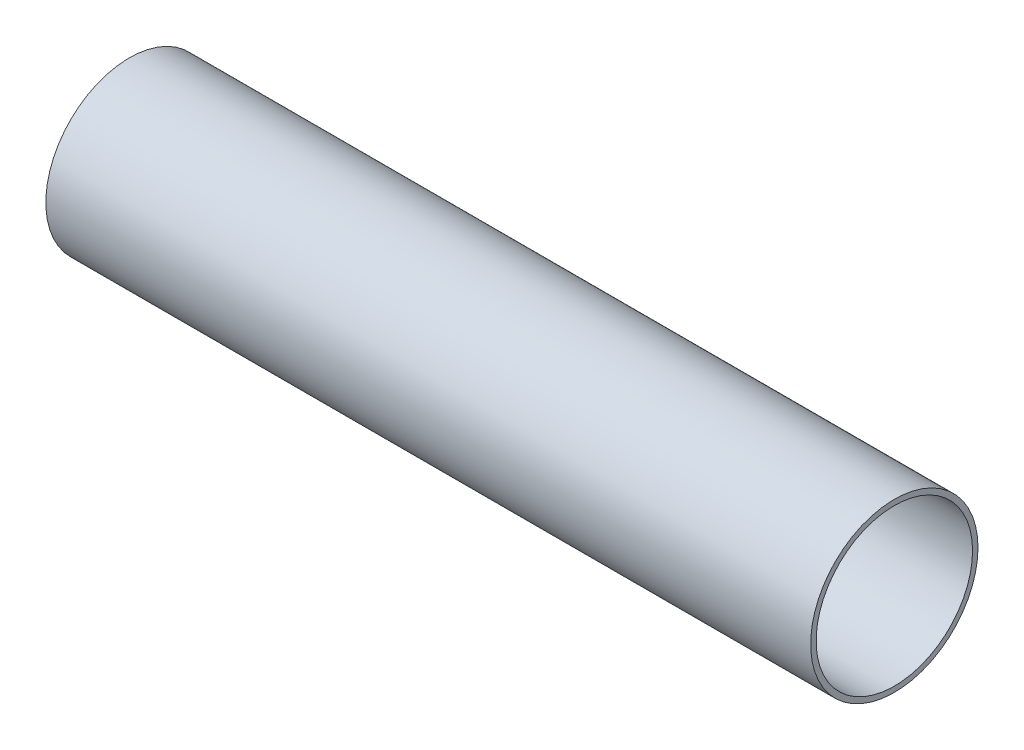
SolidWorks part; units mm, degrees
ref_plane "Front Plane" through (0, 0, 0) normal (0, 0, 1) x (1, 0, 0)
ref_plane "Top Plane" through (0, 0, 0) normal (0, 1, 0) x (1, 0, 0)
ref_plane "Right Plane" through (0, 0, 0) normal (1, 0, 0) x (0, 0, -1)
sketch "Sketch1" plane through (0, 0, 0) normal (1, 0, 0) x (0, 0, -1)
  circle A0 centre (0, 0) radius 45.847
  circle A1 centre (0, 0) radius 42.8625
  dimension "D1" = 91.694
  dimension "D2" = 85.725
extrude "Boss-Extrude1" add sketch "Sketch1" along normal blind 419.1
